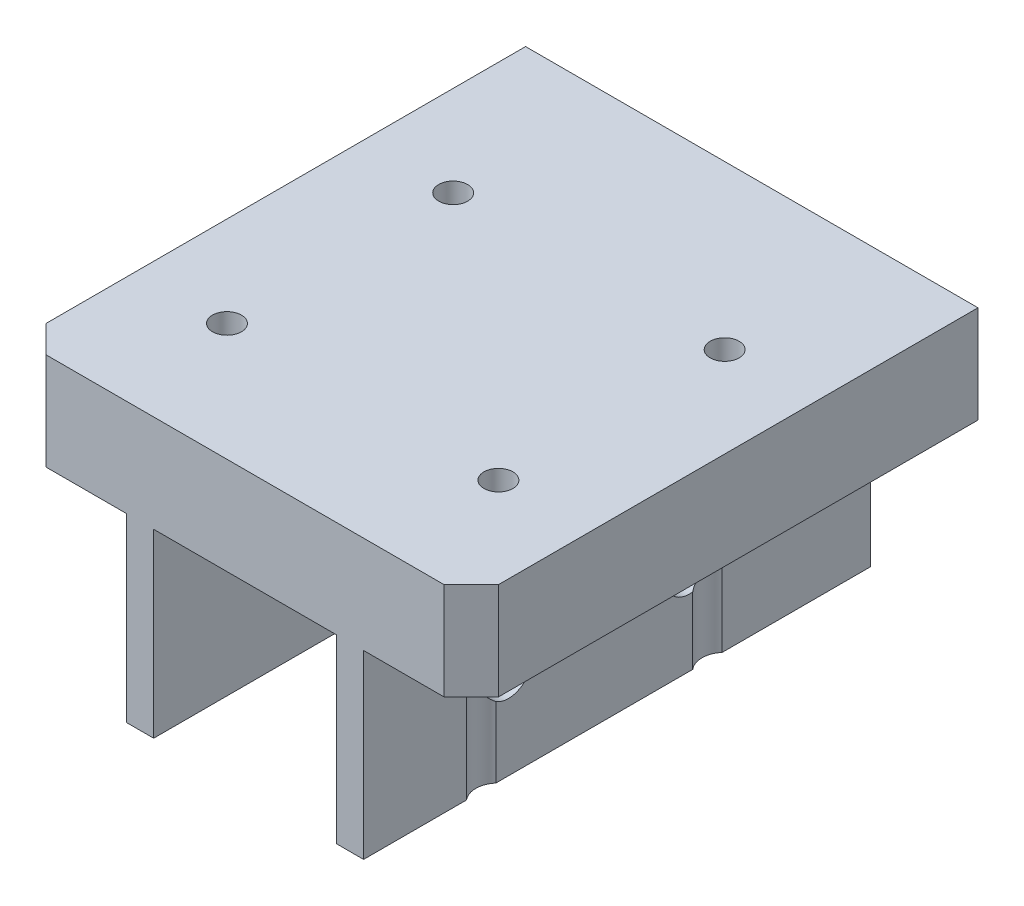
SolidWorks part; units mm, degrees
ref_plane "前视基准面" through (0, 0, 0) normal (0, 0, 1) x (1, 0, 0)
ref_plane "上视基准面" through (0, 0, 0) normal (0, 1, 0) x (1, 0, 0)
ref_plane "右视基准面" through (0, 0, 0) normal (1, 0, 0) x (0, 0, -1)
other "Configuration Table"
sketch "草图1" plane through (0, 0, 0) normal (0, 0, 1) x (1, 0, 0)
  line L2 (-13.1, -14.9614) -> (-10.1, -14.9614)
  line L3 (-25, 5.0386) -> (-25, 15.7886)
  line L4 (-25, 15.7886) -> (25, 15.7886)
  line L5 (25, 5.0386) -> (25, 15.7886)
  line L6 (-13.1, -8.2732) -> (25, 15.7886) construction
  line L7 (-25, 15.7886) -> (13.1, -8.2732) construction
  line L9 (-10.1, -14.9614) -> (-10.1, 5.0386)
  line L11 (-10.1, 5.0386) -> (10.1, 5.0386)
  line L12 (10.1, -14.9614) -> (10.1, 5.0386)
  line L13 (0, -24.3035) -> (10.1, 5.0386) construction
  line L14 (-10.1, 5.0386) -> (0, -24.3035) construction
  line L15 (10.1, -14.9614) -> (13.1, -14.9614)
  line L16 (0, 32.2459) -> (0, -44.1995) construction
  line L19 (25, 5.0386) -> (13.1, 5.0386)
  line L20 (13.1, -14.9614) -> (13.1, 5.0386)
  line L21 (-25, 5.0386) -> (-13.1, 5.0386)
  line L22 (-13.1, -14.9614) -> (-13.1, 5.0386)
  point P0 (0, 0)
  point P7 (0, -24.3035)
  dimension "D1" = 10.75
  dimension "D2" = 20
  dimension "D3" = 3
  dimension "D4" = 20.2
  dimension "D5" = 50
extrude "凸台-拉伸1" add sketch "草图1" along normal blind 53
hole_wizard "孔1" positions "草图4" profile "草图5" legacy end condition through all
sketch "草图4" plane through (0, 5.0386, 0) normal (0, -1, 0) x (-1, 0, 0)
  line L0 (25, -53) -> (25, 0) construction
  line L1 (25, 0) -> (13.1, 0) construction
  line L2 (-25, -53) -> (-25, 0) construction
  line L3 (-13.1, 0) -> (-25, 0) construction
  point P0 (15, -15)
  point P2 (15, -40)
  point P4 (-15, -15)
  point P6 (-15, -40)
  dimension "D1" = 10
  dimension "D2" = 10
  dimension "D3" = 15
  dimension "D4" = 25
  dimension "D5" = 10
  dimension "D6" = 10
  dimension "D7" = 15
  dimension "D8" = 25
sketch "草图5" plane through (-15, 5.0386, 15) normal (1, 0, 0) x (0, 0, -1)
  line L0 (0, 0) -> (0, 10.75)
  line L1 (0, 10.75) -> (1.5, 10.75)
  line L2 (1.5, 10.75) -> (1.5, 0)
  line L3 (1.5, 0) -> (0, 0)
  line L4 (0, 110) -> (0, -10) construction
  dimension "直径" = 3
  dimension "深度" = 10.75
sketch "草图6" plane through (0, 5.0386, 0) normal (0, -1, 0) x (1, 0, 0)
  circle A0 centre (15, 40) radius 2.5
  circle A1 centre (15, 15) radius 2.5
  circle A2 centre (-15, 15) radius 2.5
  circle A3 centre (-15, 40) radius 2.5
  dimension "D1" = 5
  dimension "D2" = 5
  dimension "D3" = 5
  dimension "D4" = 5
extrude "切除-拉伸1" cut sketch "草图6" along normal through all
chamfer "倒角1" distance 3 angle 45 2 edges at (25, 10.4136, 53) (-25, 10.4136, 53)
hole_wizard "孔2" positions "草图7" profile "草图8" legacy end condition through all
sketch "草图7" plane through (13.1, 0, 0) normal (1, 0, 0) x (0, 0, -1)
  line L0 (-50, 5.0386) -> (0, 5.0386) construction
  line L1 (-53, 5.0386) -> (-41.6248, 5.0386) construction
  line L2 (0, -14.9614) -> (0, 5.0386) construction
  line L3 (-53, -14.9614) -> (-53, 5.0386) construction
  point P0 (-17, -4.9614)
  point P2 (-37, -4.9614)
  dimension "D1" = 10
  dimension "D2" = 10
  dimension "D3" = 17
  dimension "D4" = 16
sketch "草图8" plane through (13.1, -4.9614, 17) normal (0, 1, 0) x (0, 0, -1)
  line L0 (0, 0) -> (0, 38.1)
  line L1 (0, 38.1) -> (2.6, 38.1)
  line L2 (2.6, 38.1) -> (2.6, 0)
  line L3 (2.6, 0) -> (0, 0)
  line L4 (0, 110) -> (0, -10) construction
  dimension "直径" = 5.2
  dimension "深度" = 38.1
hole_wizard "M3 十字槽沉头木螺钉的锥形沉头孔1" positions "草图9" profile "草图10" countersink size "M3" standard "GB" end condition through all
sketch "草图9" plane through (0, 5.0386, 0) normal (0, -1, 0) x (-1, 0, 0)
  point P0 (-15, -15)
  point P3 (15, -15)
  point P6 (15, -40)
  point P9 (-15, -40)
sketch "草图10" plane through (15, 5.0386, 15) normal (1, 0, 0) x (0, 0, -1)
  line L0 (0, 0) -> (0, 10.75)
  line L1 (0, 10.75) -> (1.6, 10.75)
  line L2 (1.6, 10.75) -> (1.6, 1.7)
  line L3 (1.6, 1.7) -> (3.3, 0)
  line L5 (3.3, 0) -> (0, 0)
  line L6 (-1.6, 1.7) -> (-3.3, 0) construction
  line L11 (0, -6.35) -> (0, 107.95) construction
  dimension "通孔孔直径" = 3.2
  dimension "通孔孔深度" = 10.75
  dimension "近端锥形沉头孔直径" = 6.6
  dimension "近端锥形沉头孔角度" = 90
sketch "草图11" plane through (0, 5.0386, 0) normal (0, -1, 0) x (1, 0, 0)
  circle A0 centre (15, 40) radius 3.3
  circle A1 centre (15, 15) radius 3.3
  circle A2 centre (-15, 15) radius 3.3
  circle A3 centre (-15, 40) radius 3.3
extrude "切除-拉伸2" cut sketch "草图11" along normal through all draft 9
sketch "草图12" plane through (0, 0, 0) normal (0, 0, -1) x (-1, 0, 0)
  line L0 (-10.1, 5.0386) -> (10.1, 5.0386)
  line L1 (-25, 15.7886) -> (25, 15.7886)
  line L2 (-25, 15.7886) -> (-25, 5.0386)
  line L3 (-25, 5.0386) -> (-13.1, 5.0386)
  line L4 (25, 15.7886) -> (25, 5.0386)
  line L6 (-13.1, 5.0386) -> (-13.1, -14.9614)
  line L7 (-13.1, -14.9614) -> (-10.1, -14.9614)
  line L8 (-10.1, 5.0386) -> (-10.1, -14.9614)
  line L9 (13.1, -14.9614) -> (10.1, -14.9614)
  line L10 (13.1, -14.9614) -> (13.1, 5.0386)
  line L12 (10.1, -14.9614) -> (10.1, 5.0386)
  line L13 (13.1, 5.0386) -> (25, 5.0386)
extrude "凸台-拉伸2" add sketch "草图12" along normal blind 3
